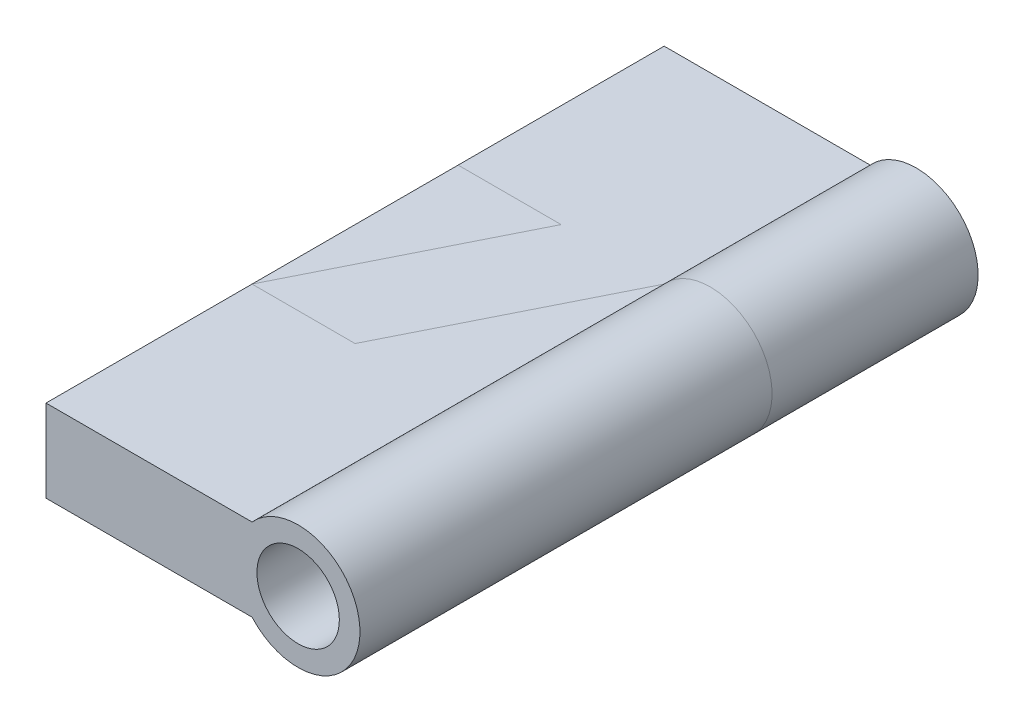
SolidWorks part; units mm, degrees
ref_plane "前视基准面" through (0, 0, 0) normal (0, 0, 1) x (1, 0, 0)
ref_plane "上视基准面" through (0, 0, 0) normal (0, 1, 0) x (1, 0, 0)
ref_plane "右视基准面" through (0, 0, 0) normal (1, 0, 0) x (0, 0, -1)
other "Configuration Table"
sketch "草图1" plane through (0, 0, 0) normal (0, 0, 1) x (1, 0, 0)
  line L1 (-6.118, 1) -> (-1.118, 1)
  line L2 (-6.118, 1) -> (-6.118, -1)
  line L3 (-6.118, -1) -> (-1.118, -1)
  line L5 (-6.118, 1) -> (-1.118, -1) construction
  line L6 (-6.118, -1) -> (-1.118, 1) construction
  arc A0 (-1.118, -1) -> (-1.118, 1) centre (0, 0) ccw
  circle A1 centre (0, 0) radius 1
  point P6 (0, 0)
  point P7 (-3.618, 0)
  dimension "D1" = 3
  dimension "D2" = 2
  dimension "D3" = 5
  dimension "D4" = 2
extrude "凸台-拉伸1" add sketch "草图1" along normal blind 10
extrude "凸台-拉伸3" add sketch "草图1<2>" along normal mid plane 10 separate body
sketch "草图1<2>" plane through (0, 0, 0) normal (0, 0, 1) x (1, 0, 0) same geometry as "草图1"
